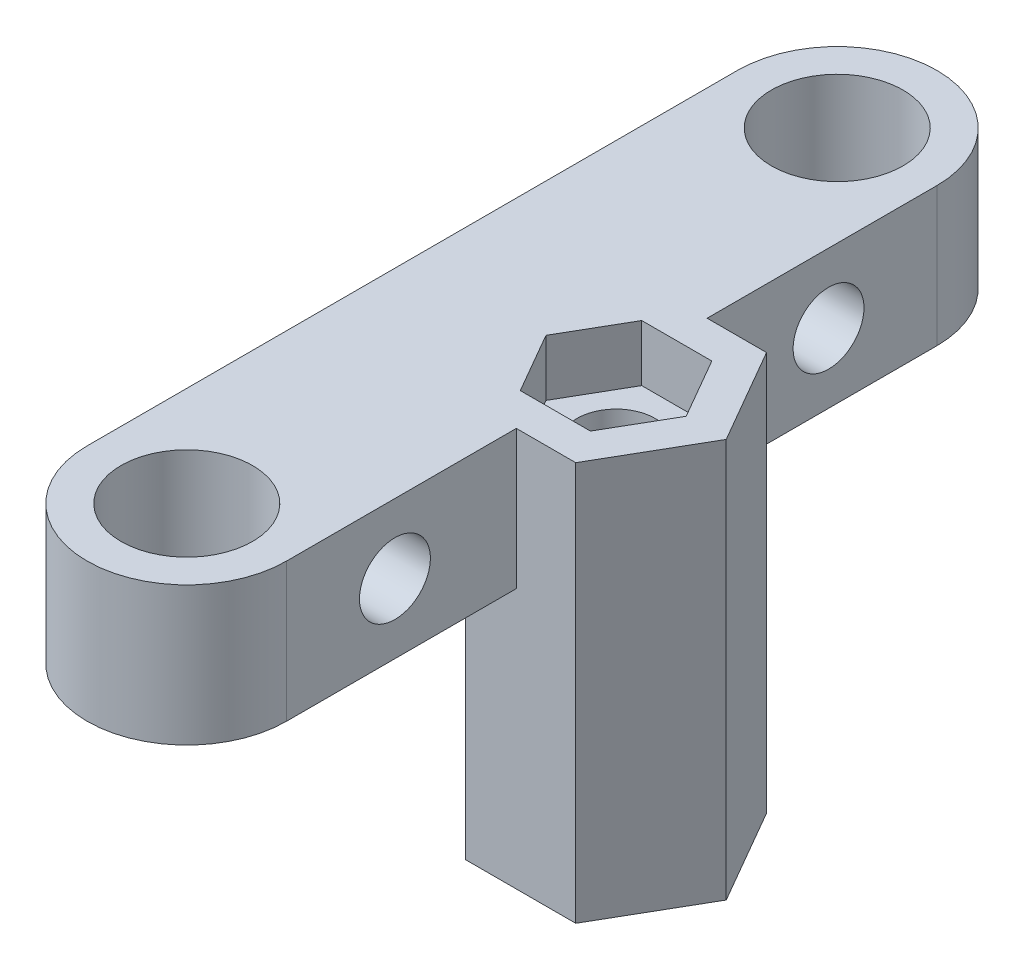
SolidWorks part; units mm, degrees
note: '?' marks a value the reader was unsure of. The reader was unsure of these and kept them because the rebuilt part matched: shared geometry of "Sketch1<6>".
material "ABS"
ref_plane "Front Plane" through (0, 0, 0) normal (0, 0, 1) x (1, 0, 0)
ref_plane "Top Plane" through (0, 0, 0) normal (0, 1, 0) x (1, 0, 0)
ref_plane "Right Plane" through (0, 0, 0) normal (1, 0, 0) x (0, 0, -1)
sketch "Sketch1" plane through (0, 0, 0) normal (0, 1, 0) x (1, 0, 0)
  line L0 (-386.3027, 0) -> (412.614, 0) construction
  line L1 (-208.5533, 25) -> (246.2338, 25) construction
  line L2 (-23.5, -33) -> (-23.5, 33)
  line L3 (8.0829, 0) -> (4.0415, 7)
  line L4 (4.0415, 7) -> (-4.0415, 7)
  line L5 (-4.0415, 7) -> (-8.0829, 0)
  line L6 (-8.0829, 0) -> (-4.0415, -7)
  line L7 (-4.0415, -7) -> (4.0415, -7)
  line L8 (4.0415, -7) -> (8.0829, 0)
  line L9 (12.7017, 0) -> (6.3509, -11)
  line L11 (-23.5, 20.9125) -> (-0.5, 20.9125)
  line L12 (-23.5, 29.0875) -> (-0.5, 29.0875)
  line L13 (-208.5533, -25) -> (246.2338, -25) construction
  line L14 (-23.5, -29.0875) -> (-0.5, -29.0875)
  line L15 (-23.5, -20.9125) -> (-0.5, -20.9125)
  line L17 (-23.5, 33) -> (-23.5, 37.5)
  line L18 (-0.5, 37.5) -> (-0.5, 33)
  line L19 (-0.5, -37.5) -> (-0.5, -33)
  line L20 (-23.5, -33) -> (-23.5, -37.5)
  line L21 (-0.5, 33) -> (-0.5, 11)
  line L22 (12.7017, 0) -> (6.3509, 11)
  line L23 (6.3509, 11) -> (-0.5, 11)
  line L24 (6.3509, -11) -> (-0.5, -11)
  line L25 (-0.5, -33) -> (-0.5, -11)
  line L28 (-6.3509, 11) -> (-12.1009, 1.0407) [skipped]
  line L29 (-12.7017, 0) -> (-6.9517, -9.9593) [skipped]
  line L30 (6.3509, -11) -> (12.1009, -1.0407) [skipped]
  line L31 (-6.3509, -11) -> (5.1491, -11) [skipped]
  circle A0 centre (0, 0) radius 7 construction
  circle A1 centre (-12, -37.5) radius 7.5875
  arc A2 (-23.5, 37.5) -> (-0.5, 37.5) centre (-12, 37.5) cw
  arc A3 (-23.5, -37.5) -> (-0.5, -37.5) centre (-12, -37.5) ccw
  circle A4 centre (0, 0) radius 11 construction
  circle A7 centre (-12, 37.5) radius 7.5875
  circle A21 centre (0, 0) radius 4.5
  point P24 (-34, 0)
  point P26 (11.5, 0)
  point P27 (-23.5, 0)
  dimension "D2" = 11.5
  dimension "D5" = 14
  dimension "D10" = 22
  dimension "D11" = 15.175
  dimension "D34" = 9
  dimension "D9" = 4
  dimension "D4" = 12
  dimension "D8" = 8.175
  dimension "D12" = 37.5
  dimension "D6" = 4.0875
  dimension "D7" = 25
extrude "Boss-Extrude1" add sketch "Sketch1" along normal blind 16
sketch "Sketch2" plane through (-23.5, 0, 0) normal (-1, 0, 0) x (0, 0, 1)
  line L0 (0, 0) -> (0, 16) construction
  line L1 (37.5, 0) -> (-37.5, 0) construction
  circle A0 centre (-25, 8) radius 4.0875
  circle A1 centre (25, 8) radius 4.0875
  dimension "D1" = 8.175
  dimension "D2" = 25
  dimension "D3" = 8
extrude "Cut-Extrude1" cut sketch "Sketch2" against normal through all
extrude "Boss-Extrude2" add sketch "Sketch1<6>" along normal blind 9.5 contours L7 L8 L3 L4 L5 L6 A21
sketch "Sketch1<6>" plane through (0, 0, 0) normal (0, 1, 0) x (1, 0, 0) same geometry as "Sketch1"
sketch "Sketch4" plane through (0, 0, 0) normal (0, -1, 0) x (1, 0, 0)
  line L0 (-23.5, 0) -> (12.7017, 0) construction
  line L1 (8.0829, 0) -> (4.0415, 7)
  line L2 (4.0415, 7) -> (-4.0415, 7)
  line L3 (-4.0415, 7) -> (-8.0829, 0)
  line L4 (-8.0829, 0) -> (-4.0415, -7)
  line L5 (-4.0415, -7) -> (4.0415, -7)
  line L6 (4.0415, -7) -> (8.0829, 0)
  line L7 (-23.5, 37.5) -> (-23.5, -37.5) construction
  line L10 (12.7017, 0) -> (6.3509, 11)
  line L11 (6.3509, 11) -> (-6.3509, 11)
  line L12 (-6.3509, 11) -> (-12.7017, 0)
  line L13 (-12.7017, 0) -> (-6.3509, -11)
  line L14 (-6.3509, -11) -> (6.3509, -11)
  line L15 (6.3509, -11) -> (12.7017, 0)
  circle A0 centre (0, 0) radius 7 construction
  circle A1 centre (0, 0) radius 11 construction
  dimension "D1" = 14
extrude "Boss-Extrude3" add sketch "Sketch4" along normal blind 30
ref_axis "Axis1" through (-34, 0, 0) along (0, 1, 0)?
ref_axis "X Axis" through (14.5118, 0, 0) along (-1, 0, 0)?
ref_axis "Y Axis" through (0, 0, -53.9) along (0, 0, 1)?
equation "\"rod_diameter\"= 8"
equation "\"rod_hole_thickness\"= 4"
equation "\"rod_radius\"= \"rod_diameter\" / 2"
equation "\"platter_diameter\"= 320"
equation "\"platter_radius\"= \"platter_diameter\" / 2"
equation "\"extruder_mount_hole_spacing\"= 75"
equation "\"arm_rod_spacing\"= 40"
equation "\"D11@Sketch1\"=\"linear_bearing_diameter\"+\"printed_hole_tolerance\""
equation "\"D12@Sketch1\"=\"z_rod_spacing\"/2"
equation "\"D1@Boss-Extrude1\" = \"rod_diameter\" + \"rod_hole_thickness\" * 2"
equation "\"motor_level_rod_spacing\"= 15"
equation "\"linear_bearing_diameter\"= 15"
equation "\"platter_rod_spacing\"= 50"
equation "\"z_rod_spacing\"= 75"
equation "\"D6@Sketch1\"=\"rod_radius\"+\"printed_hole_tolerance\"/2"
equation "\"D7@Sketch1\"=\"platter_rod_spacing\"/2"
equation "\"D2@Sketch1\"=\"linear_bearing_diameter\"/2 +\"rod_hole_thickness\""
equation "\"D8@Sketch1\"=\"rod_diameter\"+\"printed_hole_tolerance\""
equation "\"D1@Sketch2\"=\"rod_diameter\"+\"printed_hole_tolerance\""
equation "\"D2@Sketch2\"=\"platter_rod_spacing\"/2"
equation "\"D3@Sketch2\"= \"D1@Boss-Extrude1\" / 2"
equation "\"rod_nut_thickness\"= 6.5"
equation "\"rod_nut_inscribed_diameter\"= 13"
equation "\"D1@Boss-Extrude2\"= \"D1@Boss-Extrude1\" - \"rod_nut_thickness\""
equation "\"D9@Sketch1\"=\"rod_hole_thickness\""
equation "\"top_frame_spacing\"= 100"
equation "\"z_drive_rod_offset\"= 12"
equation "\"z_height\"= 400"
equation "\"gear_pitch\"=2"
equation "\"r_gear_teeth\"= 450"
equation "\"theta_gear_teeth\"= 385"
equation "\"sheet_thickness\"=5.333"
equation "\"sheet_tab_hole_thickness\"= \"sheet_thickness\""
equation "\"sheet_tab_width\"= \"sheet_thickness\"*2"
equation "\"sheet_bolt_diameter\"= 3"
equation "\"sheet_bolt_length\"= 16"
equation "\"sheet_nut_diameter\"= 5.5"
equation "\"sheet_nut_thickness\"= 2.5"
equation "\"sheet_nut_depth\"= 10"
equation "\"bearing_outside_diameter\"= 22"
equation "\"bearing_thickness\"= 7"
equation "\"corner_part_thickness\"= \"sheet_thickness\" + \"bearing_thickness\""
equation "\"setscrew_nut_diameter\"= 6"
equation "\"setscrew_nut_thickness\"= 3"
equation "\"setscrew_bolt_diameter\"= 3"
equation "\"motor_shaft_diameter\"= 5.7"
equation "\"D4@Sketch1\"=\"z_drive_rod_offset\""
equation "\"sheet_double_tab_width\"= 35"
equation "\"printed_hole_tolerance\"= 0.175"
equation "\"D5@Sketch1\"=\"rod_nut_inscribed_diameter\"+1"
equation "\"D34@Sketch1\"=\"rod_diameter\"+1"
